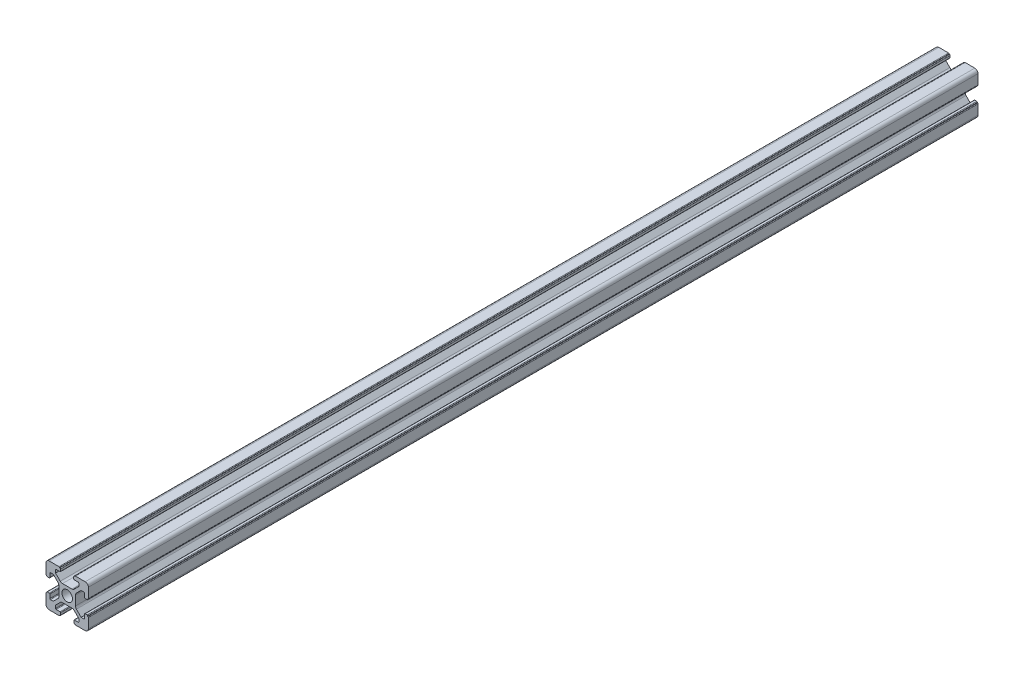
SolidWorks part; units mm, degrees
material "1060 Alloy"
ref_plane "Front Plane" through (0, 0, 0) normal (0, 0, 1) x (1, 0, 0)
ref_plane "Top Plane" through (0, 0, 0) normal (0, 1, 0) x (1, 0, 0)
ref_plane "Right Plane" through (0, 0, 0) normal (1, 0, 0) x (0, 0, -1)
sketch "Sketch1" plane through (0, 0, 0) normal (0, 0, 1) x (1, 0, 0)
  line L0 (3.8995, 3.9005) -> (10.4604, 10.4604) construction
  line L2 (-3.9002, 2.2177) -> (-3.9002, -2.2208)
  line L5 (-3.9005, 3.899) -> (3.9001, -3.8986) construction
  line L6 (-3.9, -3.901) -> (3.8995, 3.9005) construction
  line L7 (-0.0002, 10) -> (-0.0002, -9.9996) construction
  line L8 (-0.0002, -9.9996) -> (-0.0002, 10) construction
  line L9 (5.5006, 6.5619) -> (3.2793, 4.3405)
  line L14 (-10.0002, 9.9996) -> (9.9994, -10) construction
  line L15 (-9.9999, -10.0001) -> (9.9998, 10) construction
  line L16 (6.5613, 5.5012) -> (4.3401, 3.28)
  line L17 (-5.5002, 6.5603) -> (-3.279, 4.3391)
  line L18 (-6.5609, 5.4996) -> (-4.3395, 3.2783)
  line L19 (7.9206, 5.5012) -> (6.5613, 5.5012)
  line L20 (8.2006, 3.3812) -> (8.2006, 5.2212)
  line L21 (9.4206, 3.1012) -> (8.4806, 3.1012)
  line L22 (9.7006, 3.6012) -> (9.7006, 3.3812)
  line L23 (-8.5002, 9.9996) -> (-3.8802, 9.9996)
  line L24 (-3.6002, 9.7196) -> (-3.6002, 9.6996)
  line L25 (-3.6002, 9.6996) -> (-3.3802, 9.6996)
  line L26 (-3.1002, 9.4196) -> (-3.1002, 8.4796)
  line L27 (-3.3802, 8.1996) -> (-5.2202, 8.1996)
  line L28 (-5.5002, 7.9196) -> (-5.5002, 6.5603)
  line L29 (-7.9202, 5.4996) -> (-6.5609, 5.4996)
  line L30 (-8.2002, 3.3796) -> (-8.2002, 5.2196)
  line L31 (-9.4202, 3.0996) -> (-8.4802, 3.0996)
  line L32 (-9.7202, 3.5996) -> (-9.7002, 3.5996)
  line L33 (-9.7002, 3.5996) -> (-9.7002, 3.3796)
  line L34 (-10.0002, 8.4996) -> (-10.0002, 3.8796)
  line L35 (10.0006, 8.5012) -> (10.0006, 3.8812)
  line L36 (8.5006, 10.0012) -> (3.8806, 10.0012)
  line L37 (3.6006, 9.7012) -> (3.3806, 9.7012)
  line L38 (3.1006, 9.4212) -> (3.1006, 8.4812)
  line L39 (3.3806, 8.2012) -> (5.2206, 8.2012)
  line L40 (5.5006, 7.9212) -> (5.5006, 6.5619)
  line L41 (6.5629, -5.4996) -> (4.3415, -3.2783)
  line L42 (5.5022, -6.5603) -> (3.281, -4.3391)
  line L43 (5.5022, -7.9196) -> (5.5022, -6.5603)
  line L44 (3.3822, -8.1996) -> (5.2222, -8.1996)
  line L45 (3.1022, -9.4196) -> (3.1022, -8.4796)
  line L46 (3.6022, -9.6996) -> (3.3822, -9.6996)
  line L47 (8.5022, -9.9996) -> (3.8822, -9.9996)
  line L48 (10.0022, -8.4996) -> (10.0022, -3.8796)
  line L49 (9.7022, -3.5996) -> (9.7022, -3.3796)
  line L50 (9.4222, -3.0996) -> (8.4822, -3.0996)
  line L51 (8.2022, -3.3796) -> (8.2022, -5.2196)
  line L52 (7.9222, -5.4996) -> (6.5629, -5.4996)
  line L53 (-5.4986, -6.5619) -> (-3.2773, -4.3405)
  line L54 (-6.5593, -5.5012) -> (-4.3395, -3.2814)
  line L55 (-7.9186, -5.5012) -> (-6.5593, -5.5012)
  line L56 (-8.1986, -3.3812) -> (-8.1986, -5.2212)
  line L57 (-9.4186, -3.1012) -> (-8.4786, -3.1012)
  line L58 (-9.6986, -3.6012) -> (-9.6986, -3.3812)
  line L59 (-9.9986, -8.5012) -> (-9.9986, -3.8812)
  line L60 (-8.4986, -10.0012) -> (-3.8786, -10.0012)
  line L61 (-3.5986, -9.7012) -> (-3.3786, -9.7012)
  line L62 (-3.0986, -9.4212) -> (-3.0986, -8.4812)
  line L63 (-3.3786, -8.2012) -> (-5.2186, -8.2012)
  line L64 (-5.4986, -7.9212) -> (-5.4986, -6.5619)
  line L65 (-2.233, 3.8998) -> (2.2187, 3.9012)
  line L66 (3.9008, 2.234) -> (3.9022, -2.2177)
  line L67 (2.235, -3.8998) -> (-2.2167, -3.9012)
  line L68 (3.6006, 9.7212) -> (3.6006, 9.6996)
  line L69 (9.7006, 3.6012) -> (9.7206, 3.6012)
  line L70 (-9.6986, -3.6012) -> (-9.7186, -3.6012)
  line L71 (-3.5986, -9.7012) -> (-3.5986, -9.7212)
  line L72 (3.6022, -9.6996) -> (3.6022, -9.7196)
  line L73 (9.7222, -3.5996) -> (9.7022, -3.5996)
  arc A0 (-3.6002, 9.7196) -> (-3.8802, 9.9996) centre (-3.8802, 9.7196) ccw
  arc A1 (-3.3802, 9.6996) -> (-3.1002, 9.4196) centre (-3.3802, 9.4196) cw
  arc A2 (-3.1002, 8.4796) -> (-3.3802, 8.1996) centre (-3.3802, 8.4796) cw
  arc A3 (-10.0002, 8.4996) -> (-8.5002, 9.9996) centre (-8.5002, 8.4996) cw
  arc A4 (-8.2002, 3.3796) -> (-8.4802, 3.0996) centre (-8.4802, 3.3796) cw
  arc A5 (-9.4202, 3.0996) -> (-9.7002, 3.3796) centre (-9.4202, 3.3796) cw
  arc A6 (-9.7202, 3.5996) -> (-10.0002, 3.8796) centre (-9.7202, 3.8796) cw
  arc A7 (-3.279, 4.3391) -> (-2.233, 3.8998) centre (-2.2183, 5.3997) ccw
  arc A8 (-4.3395, 3.2783) -> (-3.9002, 2.2177) centre (-5.4002, 2.2177) cw
  arc A9 (-7.9202, 5.4996) -> (-8.2002, 5.2196) centre (-7.9202, 5.2196) ccw
  arc A10 (-5.2202, 8.1996) -> (-5.5002, 7.9196) centre (-5.2202, 7.9196) ccw
  arc A12 (-4.3395, -3.2814) -> (-3.9002, -2.2208) centre (-5.4002, -2.2208) ccw
  arc A13 (8.2006, 5.2212) -> (7.9206, 5.5012) centre (7.9206, 5.2212) ccw
  arc A14 (8.4806, 3.1012) -> (8.2006, 3.3812) centre (8.4806, 3.3812) cw
  arc A15 (9.7006, 3.3812) -> (9.4206, 3.1012) centre (9.4206, 3.3812) cw
  arc A16 (9.7206, 3.6012) -> (10.0006, 3.8812) centre (9.7206, 3.8812) ccw
  arc A17 (8.5006, 10.0012) -> (10.0006, 8.5012) centre (8.5006, 8.5012) cw
  arc A18 (3.6006, 9.7212) -> (3.8806, 10.0012) centre (3.8806, 9.7212) cw
  arc A19 (3.1006, 9.4212) -> (3.3806, 9.7012) centre (3.3806, 9.4212) cw
  arc A20 (3.3806, 8.2012) -> (3.1006, 8.4812) centre (3.3806, 8.4812) cw
  arc A21 (5.5006, 7.9212) -> (5.2206, 8.2012) centre (5.2206, 7.9212) ccw
  arc A22 (3.2793, 4.3405) -> (2.2187, 3.9012) centre (2.2187, 5.4012) cw
  arc A23 (4.3401, 3.28) -> (3.9008, 2.234) centre (5.4007, 2.2193) ccw
  arc A25 (5.2222, -8.1996) -> (5.5022, -7.9196) centre (5.2222, -7.9196) ccw
  arc A26 (3.1022, -8.4796) -> (3.3822, -8.1996) centre (3.3822, -8.4796) cw
  arc A27 (3.3822, -9.6996) -> (3.1022, -9.4196) centre (3.3822, -9.4196) cw
  arc A28 (3.6022, -9.7196) -> (3.8822, -9.9996) centre (3.8822, -9.7196) ccw
  arc A29 (10.0022, -8.4996) -> (8.5022, -9.9996) centre (8.5022, -8.4996) cw
  arc A30 (9.7222, -3.5996) -> (10.0022, -3.8796) centre (9.7222, -3.8796) cw
  arc A31 (9.4222, -3.0996) -> (9.7022, -3.3796) centre (9.4222, -3.3796) cw
  arc A32 (8.2022, -3.3796) -> (8.4822, -3.0996) centre (8.4822, -3.3796) cw
  arc A33 (7.9222, -5.4996) -> (8.2022, -5.2196) centre (7.9222, -5.2196) ccw
  arc A34 (4.3415, -3.2783) -> (3.9022, -2.2177) centre (5.4022, -2.2177) cw
  arc A35 (3.281, -4.3391) -> (2.235, -3.8998) centre (2.2203, -5.3997) ccw
  circle A36 centre (0.001, -0.001) radius 2.5 construction
  arc A37 (-8.1986, -5.2212) -> (-7.9186, -5.5012) centre (-7.9186, -5.2212) ccw
  arc A38 (-8.4786, -3.1012) -> (-8.1986, -3.3812) centre (-8.4786, -3.3812) cw
  arc A39 (-9.6986, -3.3812) -> (-9.4186, -3.1012) centre (-9.4186, -3.3812) cw
  arc A40 (-9.7186, -3.6012) -> (-9.9986, -3.8812) centre (-9.7186, -3.8812) ccw
  arc A41 (-8.4986, -10.0012) -> (-9.9986, -8.5012) centre (-8.4986, -8.5012) cw
  arc A42 (-3.5986, -9.7212) -> (-3.8786, -10.0012) centre (-3.8786, -9.7212) cw
  arc A43 (-3.0986, -9.4212) -> (-3.3786, -9.7012) centre (-3.3786, -9.4212) cw
  arc A44 (-3.3786, -8.2012) -> (-3.0986, -8.4812) centre (-3.3786, -8.4812) cw
  arc A45 (-5.4986, -7.9212) -> (-5.2186, -8.2012) centre (-5.2186, -7.9212) ccw
  arc A46 (-3.2773, -4.3405) -> (-2.2167, -3.9012) centre (-2.2167, -5.4012) cw
  arc A48 (-4.3381, -3.28) -> (-3.8988, -2.234) centre (-5.3987, -2.2193) ccw [skipped]
  point P0 (0, 0)
  point P9 (-0.0002, 0.0002)
  point P12 (-0.0003, -0.0003)
  point P43 (-3.6002, 9.9996)
  point P46 (-3.1002, 9.6996)
  point P49 (-3.1002, 8.1996)
  point P55 (-8.2002, 3.0996)
  point P58 (-9.7002, 3.0996)
  point P61 (-10.0002, 3.5996)
  point P64 (-2.8395, 3.8996)
  point P67 (-3.9002, 2.839)
  point P70 (-8.2002, 5.4996)
  point P73 (-5.5002, 8.1996)
  point P184 (0.001, 0)
  dimension "D14" = 0.28
  dimension "D15" = 0.28
  dimension "D16" = 0.28
  dimension "D17" = 1.5
  dimension "D18" = 0.28
  dimension "D19" = 1.5
  dimension "D20" = 1.5
  dimension "D21" = 0.28
  dimension "D23" = 5
  dimension "D27" = 1.5
  dimension "D1" = 7.8
  dimension "D2" = 7.8
  dimension "D3" = 3.1
  dimension "D4" = 3.6
  dimension "D5" = 20
  dimension "D6" = 20
  dimension "D7" = 0.75
  dimension "D8" = 1.8
  dimension "D9" = 5.5
  dimension "D10" = 6.4
  dimension "D11" = 6.4
  dimension "D12" = 3.7627
  dimension "D13" = 0.3
  dimension "D24" = 4.62
  dimension "D25" = 3.9005
  dimension "D26" = 7.801
  dimension "D22" = 4
extrude "Boss-Extrude1" add sketch "Sketch1" along normal blind 420 contours L53 A46 L67 A35 L42 L43 A25 L44 A26 L45 A27 L46 L72 A28 L47 A29 L48 A30 L73 L49 A31 L50 A32 L51 A33 L52 L41 A34 L66 A23 L16 L19 A13 L20 A14 L21 A15 L22 L69 A16 L35 A17 L36 A18 L68 L37 A19 L38 A20 region at (0.0009, 0, 0)
sketch3d "3DSketch2"
  circle A0 centre (0, 0, 0) radius 2.5
  point P2 (0, 0, 2.5)
extrude "Cut-Extrude1" cut sketch "3DSketch2" along direction (0, 0, 1) on the side of the normal through all contours A0
